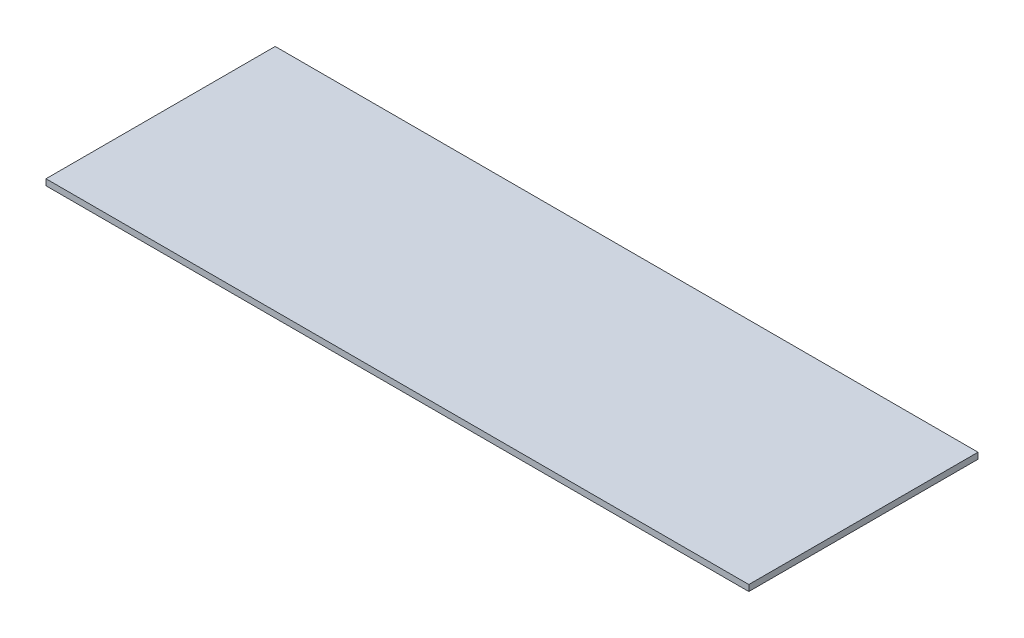
SolidWorks part; units mm, degrees
material "ABS"
ref_plane "Front Plane" through (0, 0, 0) normal (0, 0, 1) x (1, 0, 0)
ref_plane "Top Plane" through (0, 0, 0) normal (0, 1, 0) x (1, 0, 0)
ref_plane "Right Plane" through (0, 0, 0) normal (1, 0, 0) x (0, 0, -1)
sketch "Sketch1" plane through (0, 0, 0) normal (0, 1, 0) x (1, 0, 0)
  line L1 (0, 0) -> (2300, 0)
  line L2 (0, 0) -> (0, 750)
  line L3 (0, 750) -> (2300, 750)
  line L4 (2300, 0) -> (2300, 750)
  dimension "D1" = 750
  dimension "D2" = 2300
extrude "Boss-Extrude1" add sketch "Sketch1" along normal blind 20
